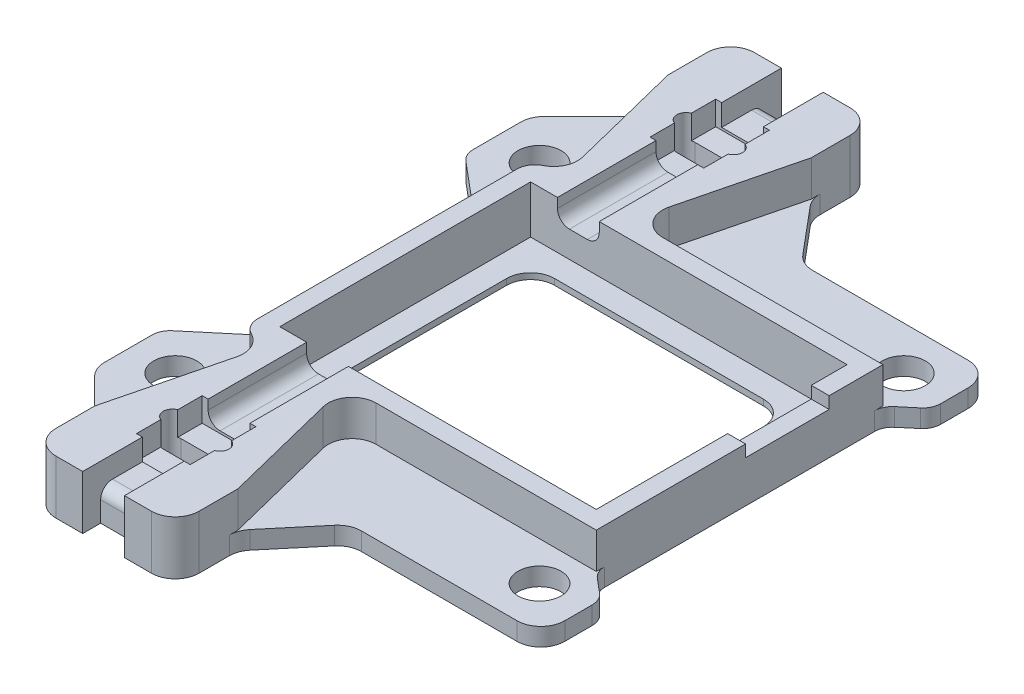
SolidWorks part; units mm, degrees
ref_plane "Ebene vorne" through (0, 0, 0) normal (0, 0, 1) x (1, 0, 0)
ref_plane "Ebene oben" through (0, 0, 0) normal (0, 1, 0) x (1, 0, 0)
ref_plane "Ebene rechts" through (0, 0, 0) normal (1, 0, 0) x (0, 0, -1)
sketch "Skizze1" plane through (0, 0, 0) normal (0, 1, 0) x (1, 0, 0)
  line L0 (0, -24) -> (0, 0) construction
  line L1 (19, 24) -> (-19, 24)
  line L2 (19, 24) -> (19, -24)
  line L3 (19, -24) -> (-19, -24)
  line L4 (-19, 24) -> (-19, -24)
  line L5 (0, 0) -> (0, 24) construction
  line L6 (-19, 0) -> (0, 0) construction
  line L7 (0, 0) -> (19, 0) construction
  point P0 (0, 0)
  dimension "D1" = 48
  dimension "D2" = 38
extrude "Grundplatte" add sketch "Skizze1" along normal blind 1.5
sketch "Skizze2" plane through (0, 1.5, 0) normal (0, 1, 0) x (1, 0, 0)
  line L0 (0, -24) -> (0, 0) construction
  line L1 (-19, -24) -> (19, -24) construction
  line L2 (0, 0) -> (0, 24) construction
  line L3 (19, 24) -> (-19, 24) construction
  line L5 (-15.25, -15.25) -> (0, -15.25) construction
  line L6 (0, -15.25) -> (15.25, -15.25) construction
  line L7 (-15.25, 15.25) -> (0, 15.25) construction
  line L8 (0, 15.25) -> (15.25, 15.25) construction
  line L9 (-19, 0) -> (0, 0) construction
  line L10 (-19, 24) -> (-19, -24) construction
  line L11 (0, 0) -> (19, 0) construction
  line L12 (19, -24) -> (19, 24) construction
  line L13 (-15.25, -15.25) -> (-15.25, 0) construction
  line L14 (-15.25, 0) -> (-15.25, 15.25) construction
  circle A0 centre (-15.25, 15.25) radius 1.8
  circle A1 centre (15.25, 15.25) radius 1.8
  circle A2 centre (15.25, -15.25) radius 1.8
  circle A3 centre (-15.25, -15.25) radius 1.8
  point P18 (0, 0)
  dimension "D3" = 3.6
  dimension "D2" = 30.5
  dimension "D1" = 4
extrude "FC-Bohrungen" cut sketch "Skizze2" against normal blind 1.5
sketch "Skizze3" plane through (0, 1.5, 0) normal (0, 1, 0) x (1, 0, 0)
  line L0 (-19, 0) -> (2, 0) construction
  line L1 (15.25, 10.5) -> (-11.25, 10.5)
  line L2 (15.25, 10.5) -> (15.25, -10.5)
  line L3 (15.25, -10.5) -> (-11.25, -10.5)
  line L4 (-11.25, 10.5) -> (-11.25, -10.5)
  line L5 (15.25, 10.5) -> (-11.25, -10.5) construction
  line L6 (15.25, -10.5) -> (-11.25, 10.5) construction
  line L7 (-19, 24) -> (-19, -24) construction
  line L8 (2, 0) -> (19, 0) construction
  line L9 (19, -24) -> (19, 24) construction
  point P0 (6.0239, -0.5281)
  dimension "D1" = 21
  dimension "D2" = 26.5
  dimension "D3" = 21
extrude "Auschnitt Empfänger" cut sketch "Skizze3" against normal through all
sketch "Skizze4" plane through (0, 0, 0) normal (0, -1, 0) x (1, 0, 0)
  line L2 (-9.25, 8.5) -> (12.25, 8.5)
  line L3 (-9.25, 8.5) -> (-9.25, -8.5)
  line L4 (-9.25, -8.5) -> (12.25, -8.5)
  line L5 (12.25, 8.5) -> (12.25, -8.5)
  line L9 (-11.25, 10.5) -> (15.25, 10.5)
  line L10 (-11.25, 10.5) -> (-11.25, -10.5)
  line L11 (-11.25, -10.5) -> (15.25, -10.5)
  line L12 (15.25, 10.5) -> (15.25, -10.5)
  dimension "D1" = 2
  dimension "D2" = 3
  dimension "D3" = 2
  dimension "D4" = 2
extrude "AuflageEMpfänger" add sketch "Skizze4" against normal blind 0.5
fillet "Verrundung1" radius 2 4 edges at (-9.25, 0.25, -8.5) (12.25, 0.25, -8.5) (12.25, 0.25, 8.5) (-9.25, 0.25, 8.5)
sketch "Skizze7" plane through (0, 1.5, 0) normal (0, 1, 0) x (1, 0, 0)
  line L0 (-9.25, 21.5) -> (-5.25, 21.5) construction
  line L1 (-9.25, 22.25) -> (-5.25, 22.25)
  line L2 (-9.25, 20.75) -> (-5.25, 20.75)
  line L3 (15.25, 10.5) -> (-11.25, 10.5) construction
  line L4 (-7.25, 10.5) -> (-7.25, 21.5) construction
  line L5 (-11.25, -10.5) -> (-11.25, 10.5) construction
  line L6 (-11.25, 10.5) -> (15.25, 10.5) construction
  line L7 (-11.25, 0) -> (15.25, 0) construction
  line L8 (-11.25, 10.5) -> (-11.25, -10.5) construction
  line L9 (15.25, -10.5) -> (15.25, 10.5) construction
  line L10 (-7.25, -10.5) -> (-7.25, -21.5) construction
  line L11 (-9.25, -21.5) -> (-7.15, -22.7) construction
  line L12 (-9.25, -21.5) -> (-7.15, -22.7) construction
  line L13 (-9.25, -21.5) -> (-7.15, -22.7) construction
  line L14 (-5.25, -21.5) -> (-9.25, -21.5) construction
  line L15 (-5.25, -22.25) -> (-9.25, -22.25)
  line L16 (-5.25, -20.75) -> (-9.25, -20.75)
  arc A0 (-9.25, 22.25) -> (-9.25, 20.75) centre (-9.25, 21.5) ccw
  arc A1 (-5.25, 20.75) -> (-5.25, 22.25) centre (-5.25, 21.5) ccw
  arc A2 (-5.25, -22.25) -> (-5.25, -20.75) centre (-5.25, -21.5) ccw
  arc A3 (-9.25, -20.75) -> (-9.25, -22.25) centre (-9.25, -21.5) ccw
  point P2 (-7.25, 21.5)
  point P26 (-7.25, -21.5)
  dimension "D1" = 4
  dimension "D2" = 1.5
  dimension "D3" = 11
  dimension "D4" = 4
extrude "LanglochKabelbinder" cut sketch "Skizze7" against normal through all
sketch "Skizze8" plane through (0, 0, 0) normal (0, -1, 0) x (1, 0, 0)
  line L0 (-19, 24) -> (19, 24) construction
  line L1 (-13.25, 24) -> (-1.25, 24)
  line L2 (-13.25, 24) -> (-13.25, 29.25)
  line L3 (-13.25, 29.25) -> (-1.25, 29.25)
  line L4 (-1.25, 24) -> (-1.25, 29.25)
  line L5 (-9.25, 22.25) -> (-5.25, 22.25) construction
  line L6 (-19, 0) -> (19, 0) construction
  line L7 (-19, -24) -> (-19, 24) construction
  line L8 (19, 24) -> (19, -24) construction
  line L9 (-1.25, -24) -> (-1.25, -29.25)
  line L10 (-13.25, -29.25) -> (-1.25, -29.25)
  line L11 (-13.25, -24) -> (-13.25, -29.25)
  line L12 (-13.25, -24) -> (-1.25, -24)
  arc A0 (-9.25, 22.25) -> (-9.25, 20.75) centre (-9.25, 21.5) ccw construction
  arc A1 (-5.25, 20.75) -> (-5.25, 22.25) centre (-5.25, 21.5) ccw construction
  dimension "D1" = 4
  dimension "D2" = 4
  dimension "D3" = 7
extrude "Aufsatz-Linear austragen7" add sketch "Skizze8" against normal through all
sketch "Skizze10" plane through (0, 1.5, 0) normal (0, 1, 0) x (1, 0, 0)
  line L1 (-11.25, 10.5) -> (15.25, 10.5)
  line L2 (-11.25, 10.5) -> (-11.25, -10.5)
  line L3 (-11.25, -10.5) -> (15.25, -10.5)
  line L4 (15.25, 10.5) -> (15.25, -10.5)
  line L5 (-12.75, 12) -> (16.75, 12)
  line L6 (-12.75, 12) -> (-12.75, -12)
  line L7 (-12.75, -12) -> (16.75, -12)
  line L8 (16.75, 12) -> (16.75, -12)
  dimension "D1" = 1.5
  dimension "D2" = 1.5
  dimension "D3" = 1.5
  dimension "D4" = 1.5
extrude "Halterahmen Empfänger" add sketch "Skizze10" along normal blind 3
sketch "Skizze11" plane through (16.75, 0, 0) normal (1, 0, 0) x (0, 0, -1)
  line L0 (-12, 4.5) -> (12, 4.5) construction
  line L1 (7.5, 4.5) -> (0.5, 4.5)
  line L2 (7.5, 4.5) -> (7.5, 3.5)
  line L3 (7.5, 3.5) -> (0.5, 3.5)
  line L4 (0.5, 4.5) -> (0.5, 3.5)
  line L5 (10.5, 0.5) -> (10.5, 4.5) construction
  line L6 (10.5, 0.5) -> (-10.5, 0.5) construction
  dimension "D1" = 3
  dimension "D2" = 7
  dimension "D3" = 3
extrude "Durchbruch Empfänger" cut sketch "Skizze11" against normal up to next
sketch "Skizze12" plane through (0, 1.5, 0) normal (0, 1, 0) x (1, 0, 0)
  line L0 (-13.25, -24) -> (-13.25, -29.25)
  line L1 (-13.25, -29.25) -> (-1.25, -29.25)
  line L2 (-1.25, -29.25) -> (-1.25, -24)
  line L3 (-1.25, -24) -> (-4.25, -12)
  line L4 (-12.75, -12) -> (16.75, -12) construction
  line L5 (-4.25, -12) -> (-10.25, -12)
  line L6 (-10.25, -12) -> (-13.25, -24)
  line L7 (-7.25, -20.75) -> (-7.25, -12) construction
  line L8 (-5.25, -20.75) -> (-9.25, -20.75) construction
  line L9 (-19, 0) -> (19, 0) construction
  line L10 (-19, 24) -> (-19, -24) construction
  line L11 (19, -24) -> (19, 24) construction
  line L12 (-7.25, 20.75) -> (-7.25, 12) construction
  line L13 (-10.25, 12) -> (-13.25, 24)
  line L14 (-4.25, 12) -> (-10.25, 12)
  line L15 (-1.25, 24) -> (-4.25, 12)
  line L16 (-1.25, 29.25) -> (-1.25, 24)
  line L17 (-13.25, 29.25) -> (-1.25, 29.25)
  line L18 (-13.25, 24) -> (-13.25, 29.25)
  dimension "D1" = 6
extrude "Verstärkung Kabelbinder" add sketch "Skizze12" along normal up to surface (3 mm away) up to face at (6.6667, 4.5, -1.3333)
fillet "Verrundung Verstärkung Kabelbinder" radius 2 4 edges at (-4.25, 3, -12) (-10.25, 3, -12) (-10.25, 3, 12) (-4.25, 3, 12)
sketch "Skizze13" plane through (0, 0, -10.5) normal (0, 0, 1) x (1, 0, 0)
  line L0 (15.25, 4.5) -> (-11.25, 4.5) construction
  line L1 (-9, 4.5) -> (-5.5, 4.5)
  line L2 (-9, 4.5) -> (-9, 2.7)
  line L3 (-9, 2.7) -> (-5.5, 2.7)
  line L4 (-5.5, 4.5) -> (-5.5, 2.7)
  line L5 (-7.25, 2.7) -> (-7.25, 4.5) construction
  line L6 (-11.25, 0.5) -> (-11.25, 4.5) construction
  line L7 (-11.25, 0.5) -> (15.25, 0.5) construction
  dimension "D1" = 4
  dimension "D2" = 3.5
  dimension "D3" = 2.2
extrude "Ausschnitt AntennenAnsatzEmpfänger" cut sketch "Skizze13" against normal through all and the other way through all
sketch "Skizze14" plane through (0, 0, 0) normal (0, -1, 0) x (1, 0, 0)
  line L0 (-5.25, 20.75) -> (-9.25, 20.75) construction
  line L1 (-5.25, 20.75) -> (-9.25, 20.75)
  line L2 (-9.25, 22.25) -> (-5.25, 22.25) construction
  line L3 (-9.25, 22.25) -> (-5.25, 22.25)
  line L4 (-5.25, -22.25) -> (-9.25, -22.25) construction
  line L5 (-9.25, -20.75) -> (-5.25, -20.75) construction
  line L6 (-5.25, -22.25) -> (-9.25, -22.25)
  line L7 (-9.25, -20.75) -> (-5.25, -20.75)
  arc A0 (-9.25, 22.25) -> (-9.25, 20.75) centre (-9.25, 21.5) ccw construction
  arc A1 (-5.25, 20.75) -> (-5.25, 22.25) centre (-5.25, 21.5) ccw construction
  arc A2 (-9.25, 22.25) -> (-9.25, 20.75) centre (-9.25, 21.5) ccw
  arc A3 (-5.25, 20.75) -> (-5.25, 22.25) centre (-5.25, 21.5) ccw
  arc A4 (-9.25, -20.75) -> (-9.25, -22.25) centre (-9.25, -21.5) ccw construction
  arc A5 (-5.25, -22.25) -> (-5.25, -20.75) centre (-5.25, -21.5) ccw construction
  arc A6 (-9.25, -20.75) -> (-9.25, -22.25) centre (-9.25, -21.5) ccw
  arc A7 (-5.25, -22.25) -> (-5.25, -20.75) centre (-5.25, -21.5) ccw
extrude "Langloch Reparatur" cut sketch "Skizze14" against normal through all
sketch "Skizze15" plane through (0, 2.7, 0) normal (0, 1, 0) x (1, 0, 0)
  line L0 (-5.5, 29.25) -> (-5.5, 22.25) construction
  line L1 (-9, 29.25) -> (-5.5, 29.25)
  line L2 (-9, 29.25) -> (-9, 27.75)
  line L3 (-9, 27.75) -> (-5.5, 27.75)
  line L4 (-5.5, 29.25) -> (-5.5, 27.75)
  line L5 (-5.5, -22.25) -> (-5.5, -29.25) construction
  line L6 (-9, -29.25) -> (-5.5, -29.25)
  line L7 (-9, -29.25) -> (-9, -27.75)
  line L8 (-9, -27.75) -> (-5.5, -27.75)
  line L9 (-5.5, -29.25) -> (-5.5, -27.75)
  dimension "D1" = 1.5
  dimension "D2" = 1.5
extrude "Schnitt-Linear austragen8" cut sketch "Skizze15" against normal through all
sketch "Skizze16" plane through (0, 4.5, 0) normal (0, 1, 0) x (1, 0, 0)
  line L0 (-10, 21.5) -> (-4.5, 21.5) construction
  line L1 (-19, 0) -> (19, 0) construction
  line L2 (-5, 18.75) -> (-9.5, 18.75)
  line L3 (-5, 18.75) -> (-5, 24.25)
  line L4 (-5, 24.25) -> (-9.5, 24.25)
  line L5 (-9.5, 18.75) -> (-9.5, 24.25)
  line L6 (-5, 18.75) -> (-9.5, 24.25) construction
  line L7 (-5, 24.25) -> (-9.5, 18.75) construction
  line L8 (-19, 24) -> (-19, -24) construction
  line L9 (19, -24) -> (19, 24) construction
  line L10 (-5, -24.25) -> (-9.5, -18.75) construction
  line L11 (-5, -18.75) -> (-9.5, -24.25) construction
  line L12 (-10, -21.5) -> (-4.5, -21.5) construction
  line L13 (-9.5, -18.75) -> (-9.5, -24.25)
  line L14 (-5, -24.25) -> (-9.5, -24.25)
  line L15 (-5, -18.75) -> (-5, -24.25)
  line L16 (-5, -18.75) -> (-9.5, -18.75)
  arc A0 (-9.25, 22.25) -> (-9.25, 20.75) centre (-9.25, 21.5) ccw construction
  arc A1 (-5.25, 20.75) -> (-5.25, 22.25) centre (-5.25, 21.5) ccw construction
  point P8 (-7.25, 21.5)
  point P25 (-7.25, -21.5)
  dimension "D1" = 5.5
  dimension "D2" = 4.5
extrude "Schnitt-Linear austragen9" cut sketch "Skizze16" against normal blind 2
sketch "Skizze17" plane through (0, 1.5, 0) normal (0, 1, 0) x (1, 0, 0)
  line L0 (16.75, 12) -> (19, 13.888)
  line L1 (16.75, -12) -> (16.75, 12) construction
  line L2 (16.75, 7.5) -> (16.75, 12) construction
  line L3 (19, -24) -> (19, 24) construction
  line L4 (19, 13.888) -> (19, -13.888)
  line L5 (19, -13.888) -> (16.75, -12)
  line L6 (16.75, -12) -> (16.75, 12)
  line L7 (-12.75, 7.5) -> (-19, 12.7444)
  line L8 (-19, 24) -> (-19, -24) construction
  line L9 (-19, 12.7444) -> (-19, -12.7444)
  line L10 (-19, -12.7444) -> (-12.75, -7.5)
  line L11 (-12.75, -7.5) -> (-12.75, 7.5)
  line L12 (-19, 0) -> (-12.75, 0) construction
  line L13 (-12.75, 12) -> (-12.75, -12) construction
  line L14 (-19, 18.25) -> (-13.25, 24)
  line L15 (-19, 24) -> (-19, -24) construction
  line L16 (-13.25, 24) -> (-19, 24)
  line L17 (-19, 24) -> (-19, 18.25)
  line L18 (-1.25, 24) -> (3.0395, 18.888)
  line L19 (3.0395, 18.888) -> (19, 18.888)
  line L20 (19, -24) -> (19, 24) construction
  line L21 (19, 18.888) -> (19, 24)
  line L22 (19, 24) -> (-1.25, 24)
  line L23 (16.75, 12) -> (-1.6884, 12) construction
  line L24 (-19, -24) -> (-19, -18.25)
  line L25 (-13.25, -24) -> (-19, -24)
  line L26 (-19, -18.25) -> (-13.25, -24)
  line L27 (19, -24) -> (-1.25, -24)
  line L28 (19, -18.888) -> (19, -24)
  line L29 (3.0395, -18.888) -> (19, -18.888)
  line L30 (-1.25, -24) -> (3.0395, -18.888)
  dimension "D1" = 130
  dimension "D2" = 130
  dimension "D3" = 130
  dimension "D4" = 130
  dimension "D5" = 15
  dimension "D6" = 45
  dimension "D7" = 130
  dimension "D8" = 5
extrude "Schnitt-Linear austragen10" cut sketch "Skizze17" against normal through all
fillet "Verrundung6" radius 1 2 edges at (-7.25, 2.7, -27.75) (-7.25, 2.7, 27.75)
fillet "Verrundung7" radius 1.5 8 edges at (19, 0.75, 13.888) (19, 0.75, -13.888) (16.75, 0.75, -12) (16.75, 0.75, 12) (-19, 0.75, 12.7444) (-12.75, 0.75, 7.5) (-19, 0.75, -12.7444) (-12.75, 0.75, -7.5)
fillet "Verrundung8" radius 1 4 edges at (-5.5, 2.7, -14.625) (-9, 2.7, -14.625) (-5.5, 2.7, 14.625) (-9, 2.7, 14.625)
fillet "Verrundung4" radius 2 14 edges at (-13.25, 2.25, 29.25) (-1.25, 2.25, 29.25) (-1.25, 2.25, -29.25) (-13.25, 2.25, -29.25) (-19, 0.75, -18.25) (3.0395, 0.75, -18.888) (19, 0.75, -18.888) (19, 0.75, 18.888) (3.0395, 0.75, 18.888) (-19, 0.75, 18.25)
fillet "Verrundung5" radius 1.5 2 edges at (-12.75, 3, 12) (-12.75, 3, -12)
